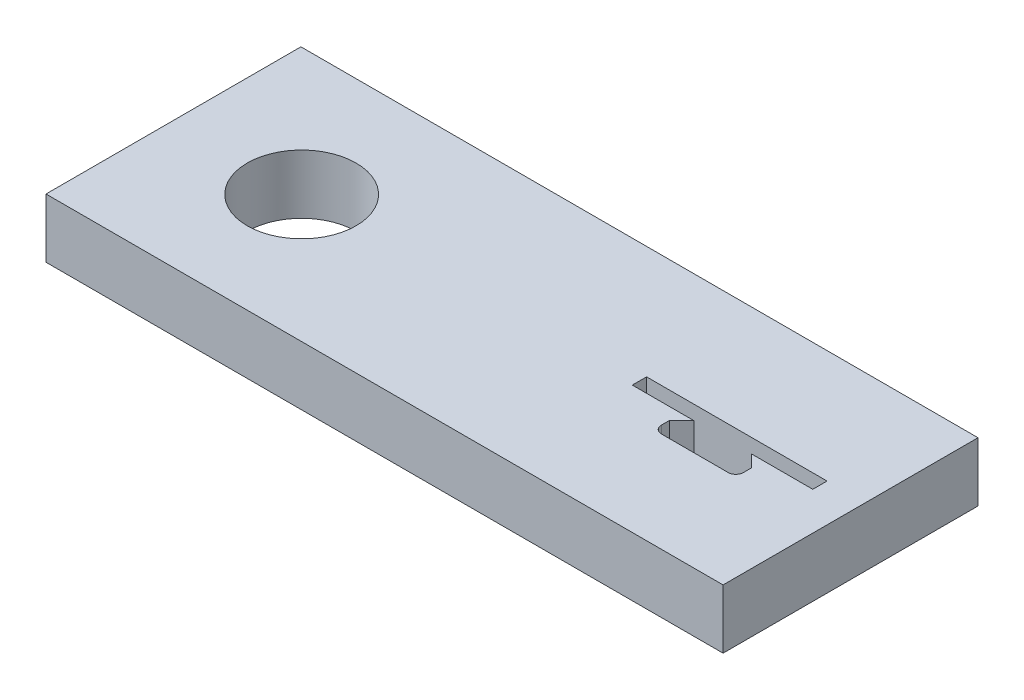
SolidWorks part; units mm, degrees
ref_plane "Front Plane" through (0, 0, 0) normal (0, 0, 1) x (1, 0, 0)
ref_plane "Top Plane" through (0, 0, 0) normal (0, 1, 0) x (1, 0, 0)
ref_plane "Right Plane" through (0, 0, 0) normal (1, 0, 0) x (0, 0, -1)
sketch "Sketch1" plane through (0, 0, 0) normal (0, 0, 1) x (1, 0, 0)
  line L0 (33.2, -62.5) -> (33.2, 62.5) construction
  line L1 (-33.2, -62.5) -> (33.2, -62.5)
  line L2 (-33.2, -62.5) -> (-33.2, -56.7)
  line L3 (-33.2, -56.7) -> (33.2, -56.7)
  line L4 (33.2, -62.5) -> (33.2, -56.7)
  dimension "D1" = 5.8
extrude "Boss-Extrude1" add sketch "Sketch1" along normal up to surface (25 mm away) contours L3 L4 L1 L2
sketch "Sketch2" plane through (0, -62.5, 0) normal (0, -1, 0) x (1, 0, 0)
  line L0 (16.6037, 14.1054) -> (16.6037, 14.0054) construction
  line L1 (17.0251, 13.2597) -> (17.658, 12.6268) construction
  line L2 (23.5287, 15.2054) -> (17.7287, 15.2054) construction
  line L3 (23.5994, 12.6268) -> (24.2322, 13.2597) construction
  line L4 (11.7787, 11.0804) -> (29.4787, 11.0804)
  line L5 (29.4787, 11.0804) -> (29.4787, 12.4804)
  line L6 (29.4787, 12.4804) -> (11.7787, 12.4804)
  line L7 (11.7787, 12.4804) -> (11.7787, 11.0804)
  line L8 (11.7787, 11.0804) -> (29.4787, 11.0804)
  line L9 (29.4787, 11.0804) -> (29.4787, 12.4804)
  line L10 (17.8044, 12.4804) -> (11.7787, 12.4804)
  line L11 (11.7787, 12.4804) -> (11.7787, 11.0804)
  line L12 (24.6537, 14.1054) -> (24.6537, 14.0054) construction
  line L13 (24.6537, 15.2054) -> (24.6537, 13.6811)
  line L14 (23.4529, 12.4804) -> (24.6537, 13.6811)
  line L15 (24.6537, 15.2054) -> (16.6037, 15.2054)
  line L16 (16.6037, 13.6811) -> (17.8044, 12.4804)
  line L17 (16.6037, 15.2054) -> (16.6037, 13.6811)
  line L18 (23.4529, 12.4804) -> (29.4787, 12.4804)
  line L19 (11.7787, 12.4804) -> (29.4787, 12.4804) construction
  circle A0 centre (-20.6287, 12.5) radius 5.335 construction
  circle A1 centre (-20.6287, 12.5) radius 5.335
  dimension "D1" = 0
extrude "Cut-Extrude1" cut sketch "Sketch2" against normal up to next contours L8 L9 L18 L14 L13 L15 L17 L16 L10 L11
fillet "Fillet1" radius 0.75 2 edges at (24.6537, -59.6, 15.2054) (16.6037, -59.6, 15.2054)
extrude "Cut-Extrude2" cut sketch "Sketch2<3>" against normal up to next contours A1
sketch "Sketch2<3>" plane through (0, -62.5, 0) normal (0, -1, 0) x (1, 0, 0) same geometry as "Sketch2"
